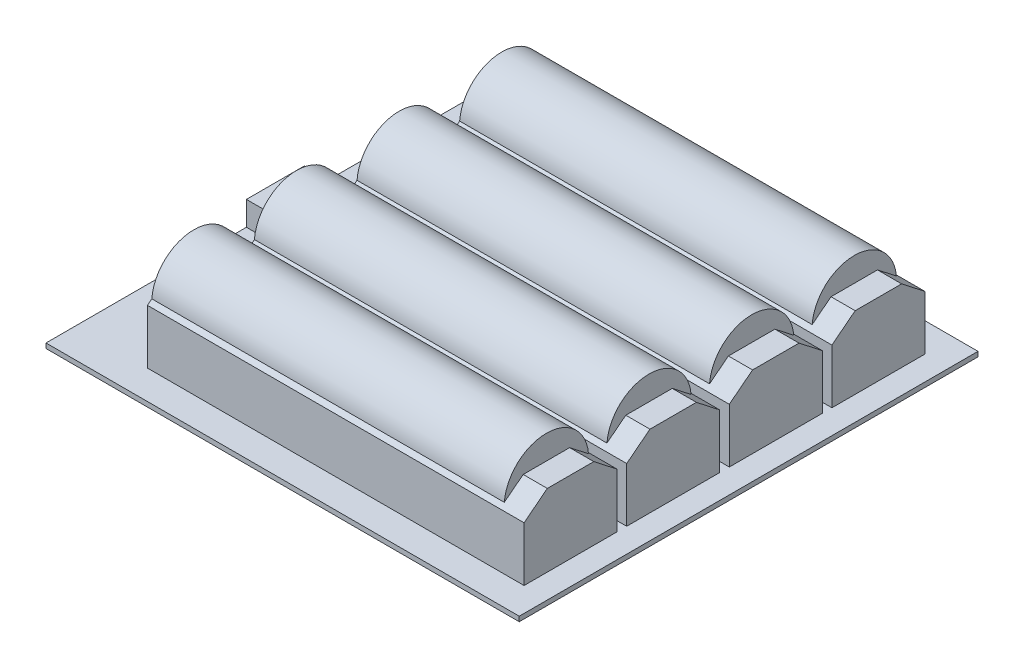
SolidWorks part; units mm, degrees
ref_plane "정면" through (0, 0, 0) normal (0, 0, 1) x (1, 0, 0)
ref_plane "윗면" through (0, 0, 0) normal (0, 1, 0) x (1, 0, 0)
ref_plane "우측면" through (0, 0, 0) normal (1, 0, 0) x (0, 0, -1)
sketch "스케치1" plane through (0, 0, 0) normal (0, 1, 0) x (1, 0, 0)
  line L1 (-49, 47.5) -> (49, 47.5)
  line L2 (-49, 47.5) -> (-49, -47.5)
  line L3 (-49, -47.5) -> (49, -47.5)
  line L4 (49, 47.5) -> (49, -47.5)
  line L5 (-49, 47.5) -> (49, -47.5) construction
  line L6 (-49, -47.5) -> (49, 47.5) construction
  point P0 (0, 0)
  dimension "D1" = 98
  dimension "D2" = 95
extrude "보스-돌출1" add sketch "스케치1" along normal blind 1
sketch "스케치2" plane through (0, 1, 0) normal (0, 1, 0) x (1, 0, 0)
  line L1 (-49, 47.5) -> (49, 47.5)
  line L2 (-49, 47.5) -> (-49, -47.5)
  line L3 (-49, -47.5) -> (49, -47.5)
  line L4 (49, 47.5) -> (49, -47.5)
  line L5 (-34, 42.5) -> (44, 42.5)
  line L6 (-34, 42.5) -> (-34, -42.5)
  line L7 (-34, -42.5) -> (44, -42.5)
  line L8 (44, 42.5) -> (44, -42.5)
  line L9 (-34, 42.5) -> (44, 42.5)
  line L10 (-34, 42.5) -> (-34, -42.5)
  line L11 (-34, -42.5) -> (44, -42.5)
  line L12 (44, 42.5) -> (44, -42.5)
  point P10 (0, 0)
  dimension "D1" = 5
  dimension "D2" = 5
  dimension "D3" = 15
  dimension "D4" = 5
  dimension "D5" = 85
  dimension "D6" = 78
extrude "보스-돌출2" add sketch "스케치2" along normal blind 20 contours L8 L5 L6 L7 region at (5, 1, 0)
sketch "스케치4" plane through (44, 0, 0) normal (1, 0, 0) x (0, 0, -1)
  line L0 (0, 21) -> (0, 1) construction
  line L1 (42.5, 21) -> (-42.5, 21) construction
  line L2 (42.5, 1) -> (-42.5, 1) construction
  line L3 (-42.5, 21) -> (0, 21) construction
  line L4 (-21.25, 21) -> (-21.25, 1) construction
  line L5 (21.25, 21) -> (21.25, 1) construction
  line L6 (-41.5, 1) -> (-22.25, 1)
  line L7 (-47.5, 1) -> (47.5, 1) construction
  line L8 (-1, 1) -> (-20.25, 1)
  line L9 (-42.5, 21) -> (-42.5, 1) construction
  line L11 (-41.5, 1) -> (-22.25, 1)
  line L12 (-41.5, 1) -> (-41.5, 12.2547)
  line L13 (-36.685, 16.0072) -> (-27.065, 16.0072)
  line L14 (-22.25, 1) -> (-22.25, 12.2547)
  line L15 (-1, 1) -> (-20.25, 1)
  line L18 (-31.875, 16.0072) -> (-31.875, 1) construction
  line L19 (-20.25, 1) -> (-20.25, 12.2547)
  line L20 (-41.5, 12.2547) -> (-36.685, 16.0072)
  line L21 (-22.25, 12.2547) -> (-27.065, 16.0072)
  line L22 (-1, 1) -> (-1, 12.2547)
  line L23 (-1, 12.2547) -> (-5.815, 16.0072)
  line L24 (-20.25, 12.2547) -> (-15.435, 16.0072)
  line L25 (-5.815, 16.0072) -> (-15.435, 16.0072)
  line L26 (22.25, 1) -> (22.25, 12.2547)
  line L27 (41.5, 1) -> (41.5, 12.2547)
  line L28 (41.5, 12.2547) -> (36.685, 16.0072)
  line L29 (22.25, 12.2547) -> (27.065, 16.0072)
  line L30 (36.685, 16.0072) -> (27.065, 16.0072)
  line L31 (1, 1) -> (1, 12.2547)
  line L32 (20.25, 1) -> (20.25, 12.2547)
  line L33 (20.25, 12.2547) -> (15.435, 16.0072)
  line L34 (1, 12.2547) -> (5.815, 16.0072)
  line L35 (5.815, 16.0072) -> (15.435, 16.0072)
  arc A0 (-23.1584, 12.9627) -> (-40.5916, 12.9627) centre (-31.875, 12.2547) ccw
  arc A1 (-19.3416, 12.9627) -> (-1.9084, 12.9627) centre (-10.625, 12.2547) cw
  arc A2 (23.1584, 12.9627) -> (40.5916, 12.9627) centre (31.875, 12.2547) cw
  arc A3 (19.3416, 12.9627) -> (1.9084, 12.9627) centre (10.625, 12.2547) ccw
  line M6 (-42.5, 1) -> (42.5, 1)
  line M7 (42.5, 1) -> (42.5, 21)
  line M8 (42.5, 21) -> (-42.5, 21)
  line M9 (-42.5, 21) -> (-42.5, 1)
  dimension "D1" = 1
  dimension "D2" = 1
extrude "컷-돌출1" cut sketch "스케치4" against normal blind 100 contours A0 L12 L20 M8 M9 M6 | L24 A1 A0 L21 L14 L19 M8 M6 | A3 A1 L23 L22 L31 L34 M8 M6 | A3 L33 L32 L26 L29 A2 M6 M8 | A2 L28 L27 M8 M6 M7 region at (44, 14.9934, 40.5935) region at (44, 14.9934, 21.25) region at (44, 14.9934, 0) region at (44, 14.9934, -21.25) region at (44, 14.9934, -40.5935)
extrude "컷-돌출2" cut sketch "스케치4<3>" against normal blind 5 contours L21 A0 L20 L13 | A1 L24 L25 L23 | L33 A3 L34 L35 | A2 L29 L30 L28 region at (44, 17.597, 31.875) region at (44, 17.597, 10.625) region at (44, 17.597, -31.875) region at (44, 17.597, -10.625)
sketch "스케치4<3>" plane through (44, 0, 0) normal (1, 0, 0) x (0, 0, -1) same geometry as "스케치4"
sketch "스케치5" plane through (0, 1, 0) normal (0, 1, 0) x (1, 0, 0)
  line L0 (-49, 47.5) -> (-49, -47.5) construction
  line L1 (-49, 6) -> (-40, 6)
  line L2 (-49, 6) -> (-49, -6)
  line L3 (-49, -6) -> (-40, -6)
  line L4 (-40, 6) -> (-40, -6)
  dimension "D1" = 41.5
  dimension "D2" = 41.5
  dimension "D3" = 9
extrude "보스-돌출3" add sketch "스케치5" along normal blind 5
sketch "스케치6" plane through (-49, 0, 0) normal (-1, 0, 0) x (0, 0, 1)
  line L0 (-6, 1) -> (6, 1) construction
  line L1 (0, 1) -> (0, 6) construction
  line L2 (-6, 6) -> (6, 6) construction
  line L3 (-5.6, 1) -> (-5.6, 5.6)
  line L4 (5.6, 1) -> (5.6, 5.6)
  line L5 (-5.6, 5.6) -> (5.6, 5.6)
  line L6 (5.1, 5.1747) -> (-5.1, 5.1747)
  line L7 (-5.1, 5.1747) -> (-5.1, 3.4256)
  line L8 (5.1, 5.1747) -> (5.1, 3.4256)
  line L9 (-5.1, 3.4256) -> (5.1, 3.4256)
  line L10 (-5.6, 1) -> (5.6, 1)
  point P12 (0, 5.6)
  point P16 (0, 5.1747)
  point P18 (0, 3.4256)
  dimension "D1" = 0.4
  dimension "D2" = 0.4
  dimension "D3" = 1.7491
  dimension "D4" = 10.2
extrude "컷-돌출4" cut sketch "스케치6" against normal blind 8
sketch "스케치7" plane through (0, 6, 0) normal (0, 1, 0) x (1, 0, 0)
  line L0 (-49, 0) -> (-40, 0) construction
  line L1 (-49, 6) -> (-49, -6) construction
  line L2 (-40, -6) -> (-40, 6) construction
  line L3 (-42.7314, 2.8369) -> (-46.2834, 2.8369)
  line L4 (-42.7314, -2.8369) -> (-46.2834, -2.8369)
  line L5 (-46.2834, 2.8369) -> (-47.2554, 2.4872)
  line L6 (-46.2834, -2.8369) -> (-47.2554, -2.4872)
  line L7 (-47.2554, 2.4872) -> (-47.2554, 1.3055)
  line L8 (-47.2554, -2.4872) -> (-47.2554, -1.3055)
  line L9 (-47.2554, 1.3055) -> (-46.3394, 0.6832)
  line L10 (-47.2554, -1.3055) -> (-46.3394, -0.6832)
  line L11 (-46.3394, 0.6832) -> (-42.7314, 0.6832)
  line L12 (-46.3394, -0.6832) -> (-42.7314, -0.6832)
  line L13 (-42.7314, 0.6832) -> (-42.7314, 0.9944)
  line L14 (-42.7314, -0.6832) -> (-42.7314, -0.9944)
  line L15 (-42.7314, 0.9944) -> (-46.3394, 0.9944)
  line L16 (-42.7314, -0.9944) -> (-46.3394, -0.9944)
  line L17 (-46.3394, 0.9944) -> (-46.9601, 1.4161)
  line L18 (-46.3394, -0.9944) -> (-46.9601, -1.4161)
  line L19 (-46.9601, 1.4161) -> (-46.9601, 2.3963)
  line L20 (-46.9601, -1.4161) -> (-46.9601, -2.3963)
  line L21 (-46.9601, 2.3963) -> (-46.3394, 2.6196)
  line L22 (-46.9601, -2.3963) -> (-46.3394, -2.6196)
  line L23 (-46.3394, 2.6196) -> (-42.7314, 2.6196)
  line L24 (-46.3394, -2.6196) -> (-42.7314, -2.6196)
  line L25 (-42.7314, 2.6196) -> (-42.7314, 2.8369)
  line L26 (-42.7314, -2.6196) -> (-42.7314, -2.8369)
extrude "컷-돌출5" cut sketch "스케치7" against normal blind 0.5
